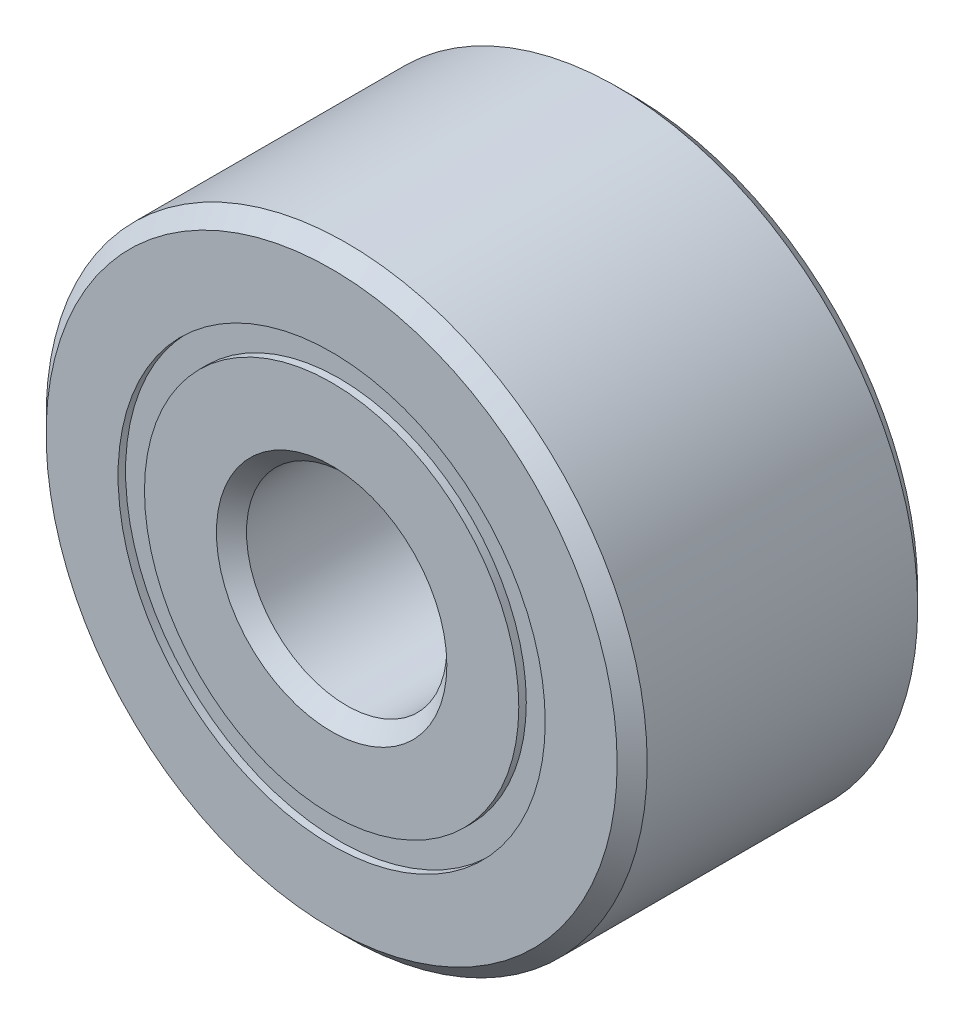
SolidWorks part; units mm, degrees
ref_plane "Front Plane" through (0, 0, 0) normal (0, 0, 1) x (1, 0, 0)
ref_plane "Top Plane" through (0, 0, 0) normal (0, 1, 0) x (1, 0, 0)
ref_plane "Right Plane" through (0, 0, 0) normal (1, 0, 0) x (0, 0, -1)
sketch "Sketch1" plane through (0, 0, 0) normal (1, 0, 0) x (0, 0, -1)
  line L0 (-1.5, 0) -> (1.5, 0) construction
  line L1 (0, 3) -> (0, -3) construction
  line L2 (1.35, 3) -> (-1.35, 3)
  line L3 (-1.35, 3) -> (-1.5, 2.85)
  line L4 (-1.5, 2.85) -> (-1.5, 2.1319)
  line L5 (-1.5, 2.1319) -> (-0.6667, 2.1319)
  line L6 (1.5, 2.1319) -> (0.6667, 2.1319)
  line L7 (1.5, 2.85) -> (1.5, 2.1319)
  line L8 (1.35, 3) -> (1.5, 2.85)
  line L9 (0, 3) -> (0, 2) construction
  line L10 (0, 2) -> (0, 1) construction
  arc A0 (-0.6667, 2.1319) -> (0.6667, 2.1319) centre (0, 2) cw
  point P14 (0, 1)
  dimension "Width" = 3
  dimension "OD" = 6
  dimension "D1" = 45
  dimension "D2" = 0.15
  dimension "Shaft Dia" = 2
  dimension "D3" = 1.3333
  dimension "D4" = 0.1319
revolve "Revolve1" add sketch "Sketch1" angle 360 about L0
sketch "Sketch3" plane through (0, 0, 0) normal (1, 0, 0) x (0, 0, -1)
  line L0 (-1.5, 1.8681) -> (-0.6667, 1.8681)
  line L1 (0, 3) -> (0, -3) construction
  line L2 (-1.5, 2.85) -> (-1.5, 2.1319) construction
  line L3 (-1.5, 1.8681) -> (-1.5, 1.15)
  line L4 (-1.35, 3) -> (-1.5, 2.85) construction
  line L5 (-1.5, 1.15) -> (-1.35, 1)
  line L6 (-1.35, 1) -> (1.35, 1)
  line L7 (1.35, 3) -> (1.35, -3) construction
  line L8 (1.35, 1) -> (1.5, 1.15)
  line L9 (1.5, -2.85) -> (1.5, 2.85) construction
  line L10 (1.5, 1.15) -> (1.5, 1.8681)
  line L11 (1.5, 1.8681) -> (0.6667, 1.8681)
  line L13 (1.35, 3) -> (1.5, 2.85) construction
  arc A0 (0.6667, 2.1319) -> (-0.6667, 2.1319) centre (0, 2) ccw construction
  arc A1 (0.6667, 1.8681) -> (-0.6667, 1.8681) centre (0, 2) cw
revolve "Revolve3" add sketch "Sketch3" angle 360 about L0
sketch "Sketch4" plane through (0, 0, 0) normal (1, 0, 0) x (0, 0, -1)
  line L0 (-0.6796, 2) -> (0.6796, 2)
  arc A2 (-0.6796, 2) -> (0.6796, 2) centre (0, 2) cw
  arc A3 (0.6667, 2.1319) -> (-0.6667, 2.1319) centre (0, 2) ccw construction
revolve "Revolve4" add sketch "Sketch4" angle 360 about L0
ref_axis "Axis1" through (0, 0, -1.5) along (0, 0, 1)
pattern_circular "CirPattern1" count 12 over 360 about axis through (0, 0, -1.5) along (0, 0, 1) of bodies 104
sketch "Sketch5" plane through (0, 0, 0) normal (1, 0, 0) x (0, 0, -1)
  line L0 (-1.5, 2.1319) -> (-0.6667, 2.1319) construction
  line L1 (-1.425, 2.1319) -> (-0.6796, 2.1319)
  line L2 (-1.425, 2.1319) -> (-1.425, 1.8681)
  line L3 (-1.425, 1.8681) -> (-0.6796, 1.8681)
  line L4 (-0.6796, 2.1319) -> (-0.6796, 1.8681)
  line L5 (-1.5, 1.8681) -> (-0.6667, 1.8681) construction
  line L6 (1.5, 2.1319) -> (0.6667, 2.1319) construction
  line L7 (1.425, 2.1319) -> (0.6796, 2.1319)
  line L8 (1.425, 2.1319) -> (1.425, 1.8681)
  line L9 (1.425, 1.8681) -> (0.6796, 1.8681)
  line L10 (0.6796, 2.1319) -> (0.6796, 1.8681)
  line L11 (1.5, 1.8681) -> (0.6667, 1.8681) construction
  line L12 (-1.35, 3) -> (-1.5, 2.85) construction
  point P18 (-1.425, 2.925)
revolve "Revolve5" add sketch "Sketch5" angle 360 about L0
sketch "Sketch6" plane through (0, 0, 0) normal (1, 0, 0) x (0, 0, -1)
  line L0 (1.5, 0) -> (-1.5, 0) construction
  line L1 (1.5, 2.1319) -> (0.4, 2.1319)
  line L2 (1.5, 2.1319) -> (1.5, 9.5)
  line L3 (1.5, 9.5) -> (0.4, 9.5)
  line L4 (0.4, 2.1319) -> (0.4, 9.5)
  dimension "Th" = 1.1
  dimension "Flange OD" = 19
revolve "Revolve6" [suppressed] add sketch "Sketch6" angle 360 about L0
equation "\"D2@Sketch1\" = \"Width@Sketch1\"*.05"
equation "\"D3@Sketch1\" = \"Width@Sketch1\"/2.25"
equation "\"D4@Sketch1\" = (((\"OD@Sketch1\"-\"Width@Sketch1\")/2)/3.25)/3.5"
equation "\"D2@CirPattern1\" = 360/\"Balls@CirPattern1\""
